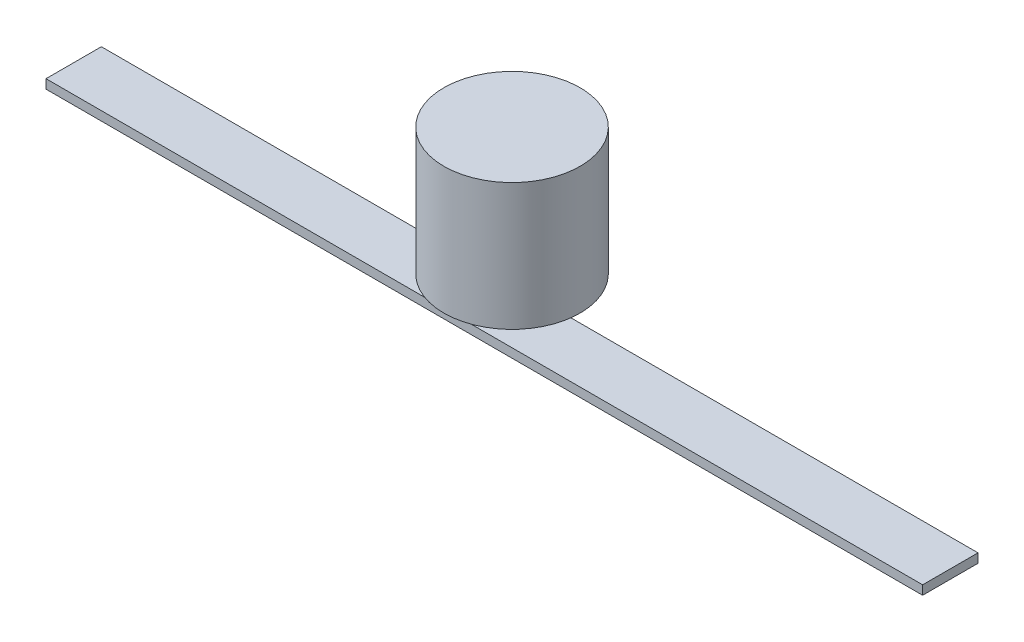
SolidWorks part; units mm, degrees
ref_plane "Front Plane" through (0, 0, 0) normal (0, 0, 1) x (1, 0, 0)
ref_plane "Top Plane" through (0, 0, 0) normal (0, 1, 0) x (1, 0, 0)
ref_plane "Right Plane" through (0, 0, 0) normal (1, 0, 0) x (0, 0, -1)
sketch "Sketch1" plane through (0, 0, 0) normal (0, 1, 0) x (1, 0, 0)
  line L1 (-241.3, -15.24) -> (241.3, -15.24)
  line L2 (-241.3, -15.24) -> (-241.3, 15.24)
  line L3 (-241.3, 15.24) -> (241.3, 15.24)
  line L4 (241.3, -15.24) -> (241.3, 15.24)
  line L5 (-241.3, -15.24) -> (241.3, 15.24) construction
  line L6 (-241.3, 15.24) -> (241.3, -15.24) construction
  point P0 (0, 0)
  dimension "D1" = 482.6
  dimension "D2" = 30.48
extrude "Boss-Extrude1" add sketch "Sketch1" along normal blind 5
sketch "Sketch2" plane through (0, 5, 0) normal (0, 1, 0) x (1, 0, 0)
  circle A0 centre (0, 0) radius 7.5
  dimension "D1" = 15
extrude "Boss-Extrude2" add sketch "Sketch2" along normal blind 20
sketch "Sketch3" plane through (0, 25, 0) normal (0, 1, 0) x (1, 0, 0)
  circle A0 centre (0, 0) radius 37.5
  dimension "D1" = 75
extrude "Boss-Extrude3" add sketch "Sketch3" along normal blind 70
